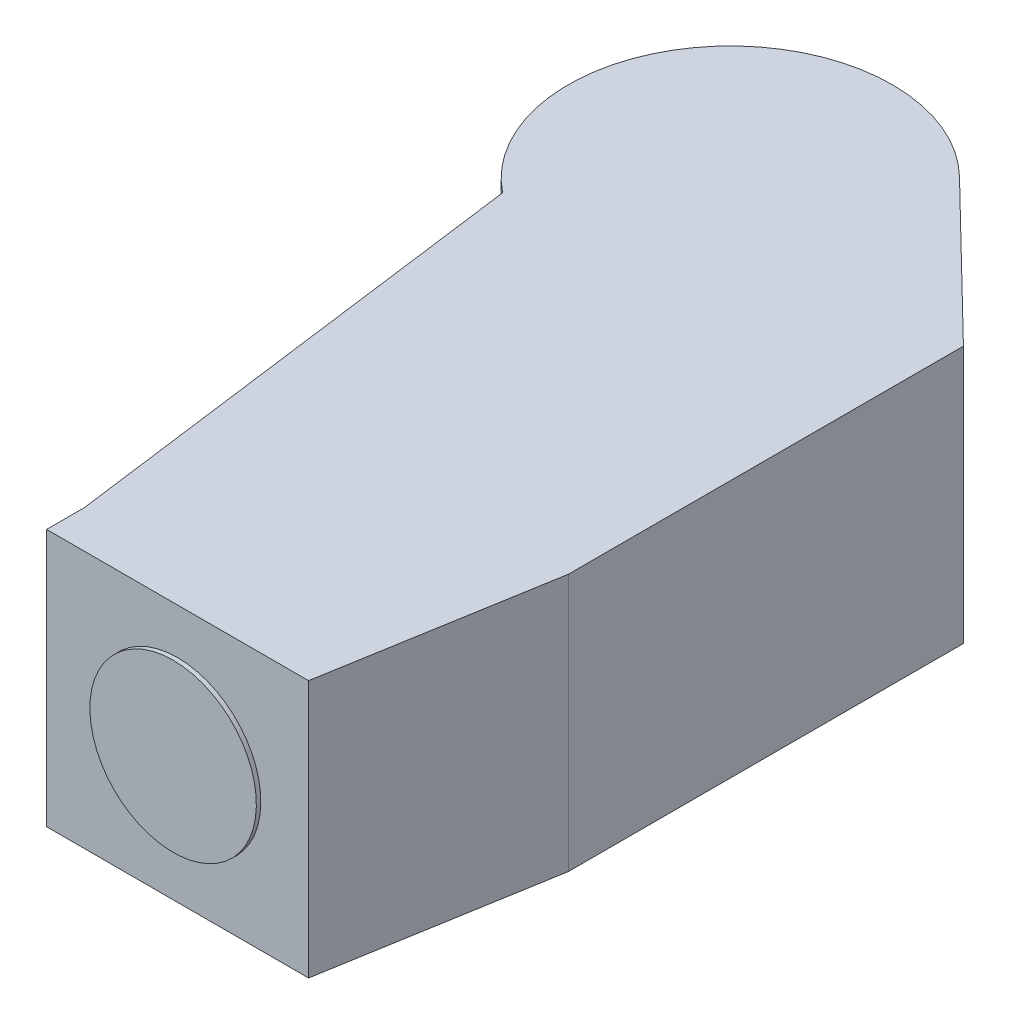
SolidWorks part; units mm, degrees
ref_plane "Front Plane" through (0, 0, 0) normal (0, 0, 1) x (1, 0, 0)
ref_plane "Top Plane" through (0, 0, 0) normal (0, 1, 0) x (1, 0, 0)
ref_plane "Right Plane" through (0, 0, 0) normal (1, 0, 0) x (0, 0, -1)
sketch "Sketch1" plane through (0, 0, 0) normal (0, 0, 1) x (1, 0, 0)
  line L0 (0, 0) -> (291, 0) construction
  line L1 (291, 0) -> (291, 17)
  line L2 (291, 17) -> (274, 17)
  line L3 (274, 17) -> (57, 45.607)
  line L4 (291, 0) -> (291, -101)
  line L5 (291, -101) -> (191, -118)
  line L6 (191, -118) -> (13, -118)
  line L7 (13, -118) -> (-52.3049, -50.9234)
  arc A0 (57, 45.607) -> (-52.3049, -50.9234) centre (0, 0) ccw
  dimension "D1" = 146
  dimension "D2" = 291
  dimension "D3" = 17
  dimension "D4" = 217
  dimension "D5" = 17
  dimension "D6" = 101
  dimension "D7" = 118
  dimension "D8" = 100
  dimension "D9" = 178
extrude "Boss-Extrude1" add sketch "Sketch1" along normal mid plane 116
sketch "Sketch2" plane through (291, 0, 0) normal (1, 0, 0) x (0, 0, -1)
  circle A0 centre (0, -42) radius 37.5
  dimension "D1" = 75
extrude "Boss-Extrude2" add sketch "Sketch2" along normal blind 2
sketch "Sketch3" plane through (293, 0, 0) normal (1, 0, 0) x (0, 0, -1)
  point P0 (0, -42)
sketch "Sketch5" plane through (0, 0, 0) normal (0, 0, 1) x (1, 0, 0)
  line L1 (346.4275, -42) -> (-102.0646, -42) construction
  point P6 (0, -42)
sketch "Sketch7" plane through (293, 0, 0) normal (1, 0, 0) x (0, 0, -1)
  point P0 (0, -42)
move or copy body "Body-Move/Copy1" bodies to move or copy 102 copy no translate (-293, 42, 0) parameters "D1"=0, "D2"=0, "D3"=0
move or copy body "Body-Move/Copy2" bodies to move or copy 103 copy no rotation origin (0, 0, 0) rotation axis (0.5774, -0.5774, 0.5774) rotation angle 120
sketch "Sketch8" plane through (0, 0, 0) normal (0, 1, 0) x (1, 0, 0)
  point P0 (-42, 293)
ref_axis "Axis1" through (-42, -99.008, -293) along (0, 1, 0)
ref_axis "Axis2" through (0, 0, 8.9044) along (0, 0, -1)
ref_plane "Plane1" through (0, 0, 0) normal (0, 1, 0) x (-1, 0, 0)
sketch "Sketch9" plane through (0, 0, 0) normal (0, 1, 0) x (-1, 0, 0)
  line L0 (71.9054, -293) -> (-19.4274, -293) construction
  line L1 (0, 8.9044) -> (0, -409.1827) construction
  line L2 (0, -270.5748) -> (0, -317.3751) construction
  point P8 (0, -293)
  point P9 (0, 0)
